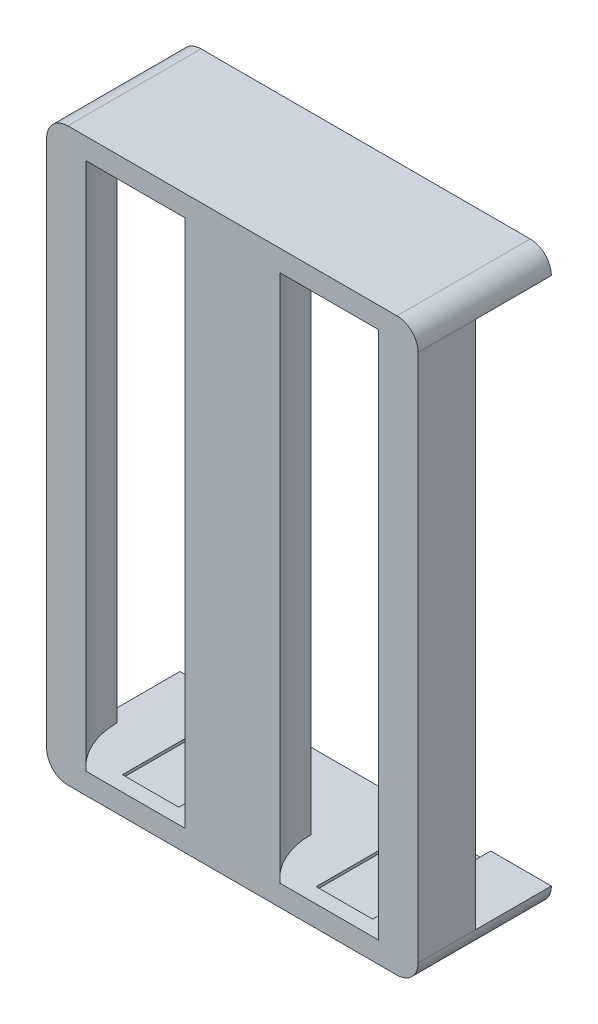
SolidWorks part; units mm, degrees
note: The reader was unsure of these and kept them because the rebuilt part matched: shared geometry of "Sketch1<3>".
ref_plane "Front Plane" through (0, 0, 0) normal (0, 0, 1) x (1, 0, 0)
ref_plane "Top Plane" through (0, 0, 0) normal (0, 1, 0) x (1, 0, 0)
ref_plane "Right Plane" through (0, 0, 0) normal (1, 0, 0) x (0, 0, -1)
sketch "Sketch1" plane through (0, 0, 0) normal (0, 1, 0) x (1, 0, 0)
  line L0 (26.35, 0) -> (26.35, 11.15)
  line L1 (0, 0) -> (52.7, 0)
  line L2 (0, 0) -> (0, 21.9)
  line L4 (52.7, 0) -> (52.7, 21.9)
  line L5 (26.35, 11.15) -> (29.35, 11.15)
  line L6 (26.35, 11.15) -> (23.35, 11.15)
  line L7 (12.6, 0.4) -> (12.6, 0)
  line L8 (1.85, 11.15) -> (0, 11.15)
  line L9 (50.85, 11.15) -> (52.7, 11.15)
  line L10 (0, 21.9) -> (52.7, 21.9)
  line L11 (52.7, 0) -> (52.7, 3)
  line L12 (52.7, 3) -> (0, 3)
  circle A0 centre (12.6, 11.15) radius 10.75
  circle A1 centre (40.1, 11.15) radius 10.75
  dimension "D2" = 21.5
  dimension "D3" = 21.5
  dimension "D1" = 52.7
  dimension "D4" = 3
  dimension "D5" = 3
  dimension "D6" = 0.4
extrude "Boss-Extrude1" add sketch "Sketch1" along normal blind 75 contours A1 L12 L4 L9 | A1 L5 L0 L12 | A0 L12 L0 L6 | A0 L8 L2 L12
extrude "Boss-Extrude2" add sketch "Sketch1<3>" against normal blind 3 contours A1 L9 L4 L10 | A1 | A1 L10 A0 L6 L5 | A0 | A0 L10 L2 L8 | A1 L12 L4 L9 | A1 L5 L0 L12 | A0 L12 L0 L6 | A0 L8 L2 L12
sketch "Sketch1<3>" plane through (0, 0, 0) normal (0, 1, 0) x (1, 0, 0) same geometry as "Sketch1"
sketch "Sketch4" plane through (0, 0, -21.9) normal (0, 0, -1) x (-1, 0, 0)
  line L0 (0, -0.95) -> (-12.6, -0.95) construction
  line L1 (0, -3) -> (0, 0) construction
  line L2 (0, 0) -> (-52.7, 0) construction
  line L3 (-6.475, -1.5) -> (-18.725, -1.5)
  line L4 (-6.475, -1.5) -> (-6.475, -0.4)
  line L5 (-6.475, -0.4) -> (-18.725, -0.4)
  line L6 (-18.725, -1.5) -> (-18.725, -0.4)
  line L7 (-6.475, -1.5) -> (-18.725, -0.4) construction
  line L8 (-6.475, -0.4) -> (-18.725, -1.5) construction
  line L9 (-12.6, -0.95) -> (-12.6, 0)
  line L10 (-12.6, 0) -> (-8.6, 0)
  line L11 (-8.6, 0) -> (-8.6, -0.4)
  line L12 (-12.6, 0) -> (-16.6, 0)
  line L13 (-16.6, 0) -> (-16.6, -0.4)
  dimension "D1" = 1.1
  dimension "D2" = 12.25
  dimension "D3" = 12.6
  dimension "D4" = 0.4
  dimension "D5" = 4
  dimension "D6" = 4
extrude "Cut-Extrude1" cut sketch "Sketch4" against normal blind 16.75
ref_plane "Plane2" through (26.35, 0, 0) normal (1, 0, 0) x (0, 0, -1)
ref_plane "Plane3" through (0, 37.5, 0) normal (0, 1, 0) x (1, 0, 0)
mirror "Mirror2" about plane through (26.35, 0, 0) normal (1, 0, 0) of "Cut-Extrude1"
mirror "Mirror3" about plane through (0, 37.5, 0) normal (0, 1, 0) of "Boss-Extrude2", "Mirror2", "Cut-Extrude1"
sketch "Sketch5" plane through (0, 0, -21.9) normal (0, 0, -1) x (-1, 0, 0)
  line L1 (-33.975, 76.5) -> (-18.725, 76.5)
  line L2 (-33.975, 76.5) -> (-33.975, 75.4)
  line L3 (-33.975, 75.4) -> (-18.725, 75.4)
  line L4 (-18.725, 76.5) -> (-18.725, 75.4)
extrude "Cut-Extrude2" cut sketch "Sketch5" against normal blind 2
fillet "Fillet1" radius 3 8 edges at (0, 78, -12.45) (0, 76.5, -21.9) (52.7, 76.5, -21.9) (52.7, 78, -12.45) (0, -1.5, -21.9) (52.7, -3, -12.45) (52.7, -1.5, -21.9) (0, -3, -12.45)
